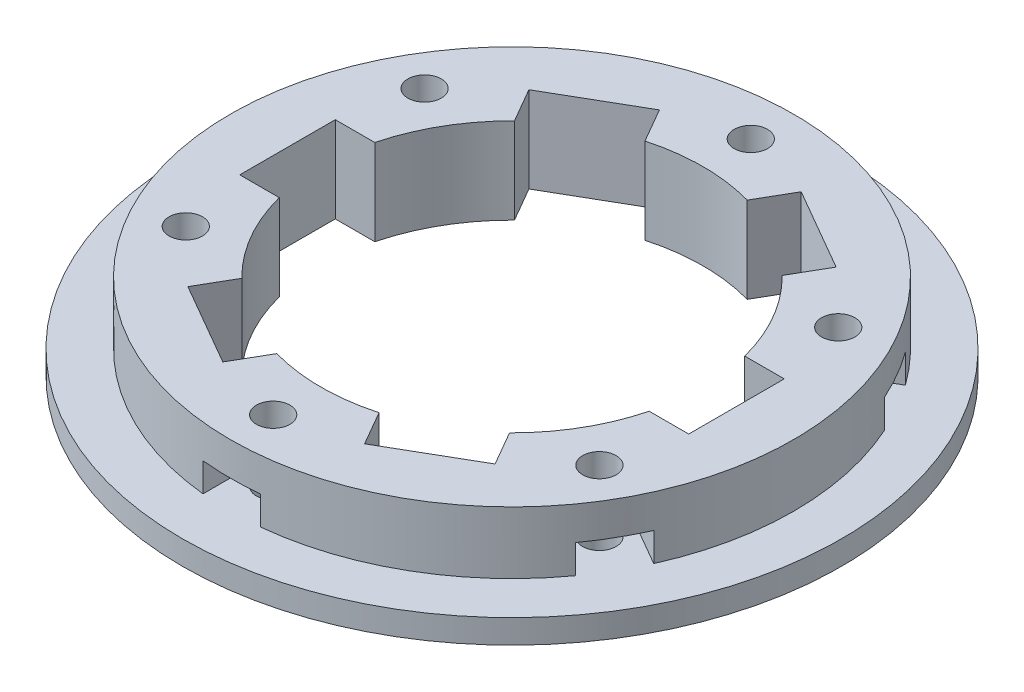
SolidWorks part; units mm, degrees
ref_plane "Front Plane" through (0, 0, 0) normal (0, 0, 1) x (1, 0, 0)
ref_plane "Top Plane" through (0, 0, 0) normal (0, 1, 0) x (1, 0, 0)
ref_plane "Right Plane" through (0, 0, 0) normal (1, 0, 0) x (0, 0, -1)
sketch "Sketch1" plane through (0, 0, 0) normal (0, 1, 0) x (1, 0, 0)
  circle A0 centre (0, 0) radius 34.5
  circle A1 centre (0, 0) radius 30 construction
  circle A2 centre (0, 0) radius 20
  dimension "D1" = 69
  dimension "D2" = 60
  dimension "D3" = 40
extrude "Boss-Extrude1" add sketch "Sketch1" along normal blind 2.5
sketch "Sketch2" plane through (0, 2.5, 0) normal (0, 1, 0) x (1, 0, 0)
  circle A0 centre (0, 0) radius 29.5
  circle A1 centre (0, 0) radius 20
  dimension "D1" = 59
  dimension "D2" = 40
extrude "Boss-Extrude2" add sketch "Sketch2" along normal blind 6.5
sketch "Sketch3" plane through (0, 9, 0) normal (0, 1, 0) x (1, 0, 0)
  line L0 (0, 0) -> (-34.5, 0) construction
  line L1 (0, 0) -> (0, -34.5) construction
  line L2 (-19.3649, 5) -> (-23.5, 5)
  line L3 (23.5, -5) -> (19.3649, -5) construction
  line L4 (23.5, -5) -> (23.5, 5) construction
  line L5 (23.5, 5) -> (19.3649, 5) construction
  line L6 (-23.5, -5) -> (-23.5, 5)
  line L7 (23.5, -5) -> (-23.5, 5) construction
  line L8 (23.5, 5) -> (-23.5, -5) construction
  line L9 (-19.3649, -5) -> (-23.5, -5)
  line L10 (-5.3523, 19.2705) -> (-7.4199, 22.8516)
  line L11 (-16.0801, 17.8516) -> (-7.4199, 22.8516)
  line L12 (-14.0126, 14.2705) -> (-16.0801, 17.8516)
  line L13 (14.0126, 14.2705) -> (16.0801, 17.8516)
  line L14 (7.4199, 22.8516) -> (16.0801, 17.8516)
  line L15 (5.3523, 19.2705) -> (7.4199, 22.8516)
  line L16 (19.3649, -5) -> (23.5, -5)
  line L17 (23.5, 5) -> (23.5, -5)
  line L18 (19.3649, 5) -> (23.5, 5)
  line L19 (5.3523, -19.2705) -> (7.4199, -22.8516)
  line L20 (16.0801, -17.8516) -> (7.4199, -22.8516)
  line L21 (14.0126, -14.2705) -> (16.0801, -17.8516)
  line L22 (-14.0126, -14.2705) -> (-16.0801, -17.8516)
  line L23 (-7.4199, -22.8516) -> (-16.0801, -17.8516)
  line L24 (-5.3523, -19.2705) -> (-7.4199, -22.8516)
  circle A0 centre (0, 0) radius 34.5 construction
  arc A1 (19.3649, -5) -> (19.3649, 5) centre (0, 0) ccw construction
  arc A2 (-19.3649, 5) -> (-19.3649, -5) centre (0, 0) ccw
  arc A3 (-5.3523, 19.2705) -> (-14.0126, 14.2705) centre (0, 0) ccw
  arc A4 (14.0126, 14.2705) -> (5.3523, 19.2705) centre (0, 0) ccw
  arc A5 (19.3649, -5) -> (19.3649, 5) centre (0, 0) ccw
  arc A6 (5.3523, -19.2705) -> (14.0126, -14.2705) centre (0, 0) ccw
  arc A7 (-14.0126, -14.2705) -> (-5.3523, -19.2705) centre (0, 0) ccw
  point P37 (0, 0)
  dimension "D1" = 47
  dimension "D3" = 40
  dimension "D2" = 10
  dimension "D4" = 6
sketch "Sketch4" plane through (0, 9, 0) normal (0, 1, 0) x (1, 0, 0)
  line L0 (0, 0) -> (-45.5771, 0) construction
  line L1 (0, 0) -> (-43.3013, -25) construction
  circle A0 centre (0, 0) radius 25 construction
  circle A1 centre (-21.6506, -12.5) radius 1.75
  circle A2 centre (-21.6506, 12.5) radius 1.75
  circle A3 centre (0, 25) radius 1.75
  circle A4 centre (21.6506, 12.5) radius 1.75
  circle A5 centre (21.6506, -12.5) radius 1.75
  circle A6 centre (0, -25) radius 1.75
  point P16 (0, 0)
  point P20 (0, 0)
  dimension "D1" = 50
  dimension "D2" = 30
  dimension "D3" = 3.5
  dimension "D4" = 6
extrude "Cut-Extrude2" cut sketch "Sketch4" against normal through all
extrude "Cut-Extrude1" cut sketch "Sketch3" against normal through all
sketch "Sketch5" plane through (0, 2.5, 0) normal (0, 1, 0) x (1, 0, 0)
  line L0 (0, 0) -> (0, 34.5) construction
  line L1 (-3, 29.5) -> (3, 29.5)
  line L2 (0, 21.5359) -> (3, 23.2679)
  line L3 (3, 23.2679) -> (3, 29.5)
  line L4 (0, 21.5359) -> (-3, 23.2679)
  line L5 (-3, 23.2679) -> (-3, 29.5)
  line L6 (18.6506, 14.2321) -> (24.0477, 17.3481)
  line L7 (18.6506, 10.7679) -> (18.6506, 14.2321)
  line L8 (18.6506, 10.7679) -> (21.6506, 9.0359)
  line L9 (0, 28.4641) -> (-1.5, 27.5981) [skipped]
  line L10 (-3, 25) -> (-3, 23.2679) [skipped]
  line L11 (-1.5, 22.4019) -> (0, 21.5359) [skipped]
  line L12 (3, 26.7321) -> (1.5, 27.5981) [skipped]
  line L13 (21.6506, 9.0359) -> (27.0477, 12.1519)
  line L14 (24.0477, 17.3481) -> (27.0477, 12.1519)
  line L15 (21.6506, -9.0359) -> (27.0477, -12.1519)
  line L16 (18.6506, -10.7679) -> (21.6506, -9.0359)
  line L17 (18.6506, -10.7679) -> (18.6506, -14.2321)
  line L18 (18.6506, -14.2321) -> (24.0477, -17.3481)
  line L19 (27.0477, -12.1519) -> (24.0477, -17.3481)
  line L20 (3, -23.2679) -> (3, -29.5)
  line L21 (0, -21.5359) -> (3, -23.2679)
  line L22 (0, -21.5359) -> (-3, -23.2679)
  line L23 (-3, -23.2679) -> (-3, -29.5)
  line L24 (3, -29.5) -> (-3, -29.5)
  line L25 (-18.6506, -14.2321) -> (-24.0477, -17.3481)
  line L26 (-18.6506, -10.7679) -> (-18.6506, -14.2321)
  line L27 (-18.6506, -10.7679) -> (-21.6506, -9.0359)
  line L28 (-21.6506, -9.0359) -> (-27.0477, -12.1519)
  line L29 (-24.0477, -17.3481) -> (-27.0477, -12.1519)
  line L30 (-21.6506, 9.0359) -> (-27.0477, 12.1519)
  line L31 (-18.6506, 10.7679) -> (-21.6506, 9.0359)
  line L32 (-18.6506, 10.7679) -> (-18.6506, 14.2321)
  line L33 (-18.6506, 14.2321) -> (-24.0477, 17.3481)
  line L34 (-27.0477, 12.1519) -> (-24.0477, 17.3481)
  circle A0 centre (0, 0) radius 34.5 construction
  circle A1 centre (0, 25) radius 3 construction
  circle A2 centre (0, 0) radius 29.5 construction
  point P12 (0, 29.5)
  point P53 (0, 0)
  dimension "D1" = 6
  dimension "D2" = 6
extrude "Cut-Extrude3" cut sketch "Sketch5" along normal blind 3
